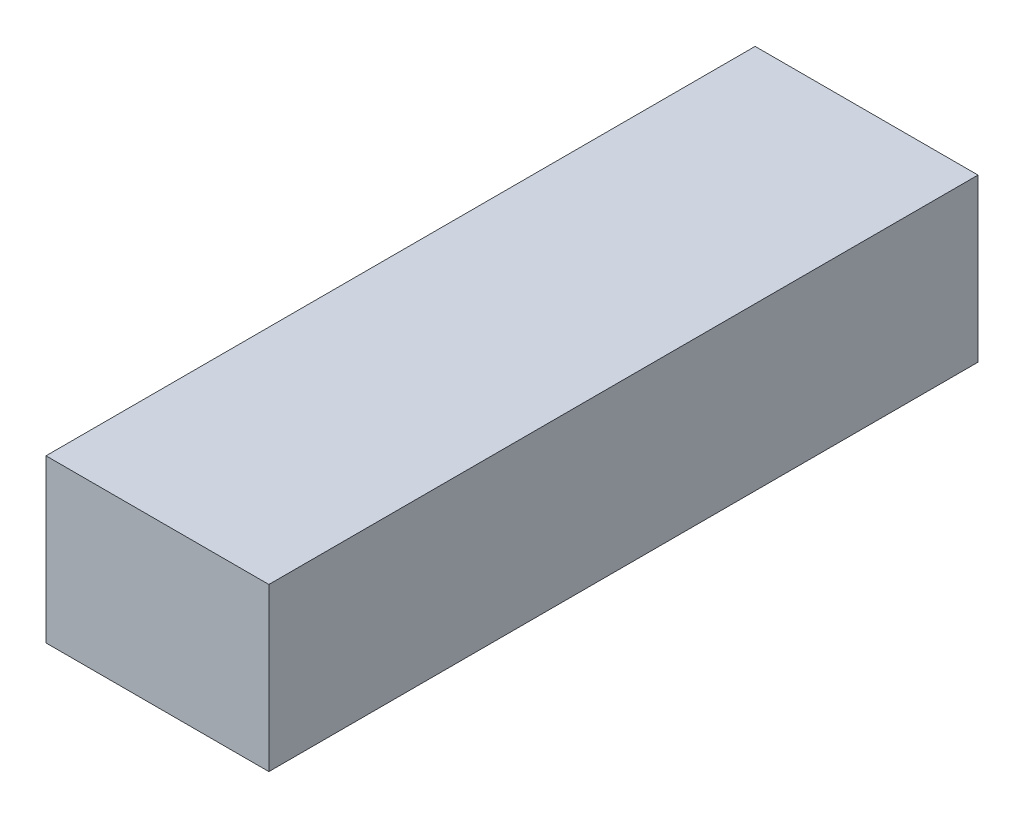
SolidWorks part; units mm, degrees
ref_plane "Front Plane" through (0, 0, 0) normal (0, 0, 1) x (1, 0, 0)
ref_plane "Top Plane" through (0, 0, 0) normal (0, 1, 0) x (1, 0, 0)
ref_plane "Right Plane" through (0, 0, 0) normal (1, 0, 0) x (0, 0, -1)
sketch "Sketch1" plane through (0, 0, 0) normal (0, 1, 0) x (1, 0, 0)
  line L0 (-573.6248, 0) -> (28107.6174, 0) construction
  line L1 (0, -573.6248) -> (0, 28107.6174) construction
  line L3 (-16.5, 52.5) -> (16.5, 52.5)
  line L4 (-16.5, 52.5) -> (-16.5, -52.5)
  line L5 (-16.5, -52.5) -> (16.5, -52.5)
  line L6 (16.5, 52.5) -> (16.5, -52.5)
  line L7 (-16.5, 52.5) -> (16.5, -52.5) construction
  line L8 (-16.5, -52.5) -> (16.5, 52.5) construction
  point P4 (0, 0)
  dimension "D1" = 33
  dimension "D2" = 105
extrude "Boss-Extrude1" add sketch "Sketch1" along normal blind 24
equation "\"Frame_Size\" = 220"
equation "\"Frame_Thickness\" = 6"
equation "\"Arm_Width\" = 30"
equation "\"Motor_Mount_Hole_Diameter\" = 8"
equation "\"Motor_Shaft_Diameter\" = 3"
equation "\"Screw_Nut_Diameter\" = 6.5"
equation "\"Screw_Diameter\" = 3"
equation "\"Screw_Shaft_Length\" = 10"
equation "\"Screw_Hole_Separation_C2C\" = 20"
equation "\"Solder_Board_Small_Screw_Hole_Separation\" = 37"
equation "\"Solder_Board_Small_Screw_Hole_Diameter\" = 3.3"
equation "\"Solder_Board_Small_Length\" = 45.72"
equation "\"Solder_Board_Small_Width\" = 33.02"
equation "\"Solder_Board_Small_Thickness\" = 1.6"
equation "\"ESC_Length\" = 35"
equation "\"ESC_Width\" = 17"
equation "\"ESC_Thickness\" = 5"
equation "\"Battery_Length\" = 105"
equation "\"Battery_Width\" = 33"
equation "\"Battery_Thickness\" = 24"
equation "\"D1@Sketch1\"=\"Battery_Width\""
equation "\"D1@Boss-Extrude1\"=\"Battery_Thickness\""
